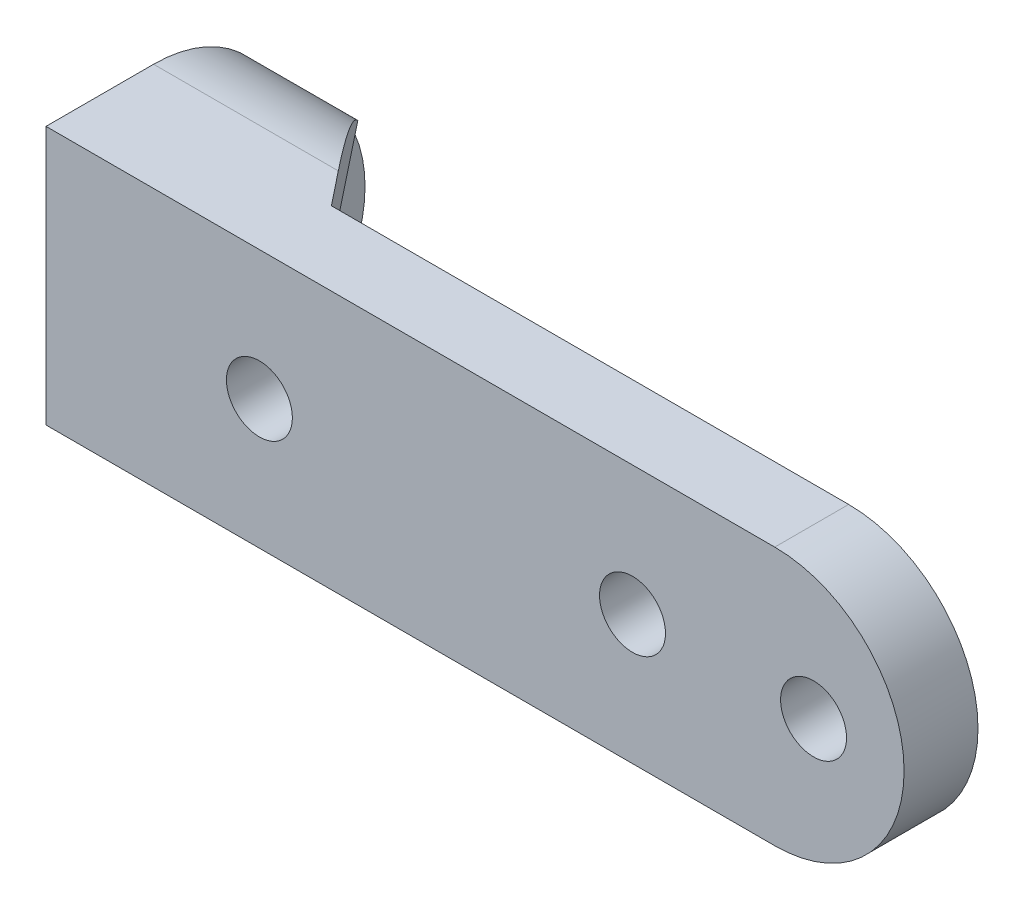
SolidWorks part; units mm, degrees
ref_plane "Front Plane" through (0, 0, 0) normal (0, 0, 1) x (1, 0, 0)
ref_plane "Top Plane" through (0, 0, 0) normal (0, 1, 0) x (1, 0, 0)
ref_plane "Right Plane" through (0, 0, 0) normal (1, 0, 0) x (0, 0, -1)
sketch "Sketch2" plane through (0, 0, 0) normal (0, 0, 1) x (1, 0, 0)
  line L0 (-20, 0) -> (20, 0) construction
  line L1 (-20, 10) -> (20, 10)
  line L2 (-20, -10) -> (20, -10)
  line L4 (-20, 10) -> (-30, 10)
  line L5 (-20, 10) -> (-20, -10)
  line L6 (-20, -10) -> (-30, -10)
  line L7 (-30, 10) -> (-30, -10)
  arc A0 (-20, 10) -> (-20, -10) centre (-20, 0) ccw
  arc A1 (20, -10) -> (20, 10) centre (20, 0) ccw
  point P2 (0, 0)
  dimension "D1" = 20
  dimension "D2" = 60
extrude "Boss-Extrude1" add sketch "Sketch2" along normal mid plane 5.715 contours A0 L4 L7 | L5 A0 | A0 L7 L6 | L2 A1 L1 L5 region at (-27.7663, 7.7663, 0) region at (3.979, 0, 0) region at (-24.2441, 0, 0) region at (-27.7663, -7.7663, 0)
sketch "Sketch3" plane through (0, 0, 2.8575) normal (0, 0, 1) x (1, 0, 0)
  line L0 (30, 0) -> (23, 0) construction
  line L1 (23, 0) -> (9, 0) construction
  circle A1 centre (9, 0) radius 2.55
  circle A2 centre (23, 0) radius 2.55
  arc A3 (20, -10) -> (20, 10) centre (20, 0) ccw construction
  dimension "D1" = 5.1
  dimension "D2" = 7
  dimension "D3" = 14
extrude "Cut-Extrude1" cut sketch "Sketch3" against normal through all both and the other way through all from surface starting at face at (-2.5, 0, 2.8575)
sketch "Sketch4" plane through (0, 0, 2.8575) normal (0, 0, 1) x (1, 0, 0)
  circle A0 centre (-19.85, 0) radius 2.55
  dimension "D1" = 5.1
  dimension "D2" = 19.85
extrude "Cut-Extrude2" cut sketch "Sketch4" against normal up to surface (5.715 mm away) up to face at (11.55, 0, -2.8575)
sketch "Sketch5" plane through (-30, 0, 0) normal (-1, 0, 0) x (0, 0, 1)
  line L0 (2.8575, -10) -> (-2.8575, -10) construction
  line L1 (2.8575, 10) -> (-15.4613, 10)
  line L2 (2.8575, 10) -> (2.8575, -10)
  line L3 (2.8575, -10) -> (-15.4613, -10)
  line L4 (-15.4613, 10) -> (-15.4613, -10)
extrude "Boss-Extrude2" add sketch "Sketch5" along normal blind 6.35
fillet "Fillet1" radius 10 2 edges at (-33.175, -10, -15.4613) (-33.175, 10, -15.4613)
sketch "Sketch6" plane through (-36.35, 0, 0) normal (-1, 0, 0) x (0, 0, 1)
  line L0 (2.8575, 10) -> (2.8575, -10) construction
  circle A0 centre (-9.1425, 0) radius 2.55
  dimension "D2" = 5.1
  dimension "D1" = 12
extrude "Cut-Extrude3" cut sketch "Sketch6" against normal through all both and the other way through all
sketch "Sketch7" plane through (0, 10, 0) normal (0, 1, 0) x (1, 0, 0)
  line L0 (-20, 2.8575) -> (-30, 15.4613)
  line L1 (20, 2.8575) -> (-30, 2.8575) construction
  line L2 (-30, 2.8575) -> (-30, 5.4613) construction
  line L3 (-30, 5.4613) -> (-30, 15.4613) construction
  line L4 (20, 2.8575) -> (-30, 2.8575)
  line L5 (-30, 2.8575) -> (-30, 5.4613)
  line L6 (-30, 5.4613) -> (-30, 15.4613)
  line M1 (-30, 2.8575) -> (-30, 5.4613)
  line M6 (20, 2.8575) -> (-30, 2.8575)
  dimension "D1" = 10
extrude "Boss-Extrude3" add sketch "Sketch7" against normal blind 3.175 contours L6 L0 M1 M6 region at (-26.6667, 10, -7.0588)
mirror "Mirror1" about plane through (0, 0, 0) normal (0, 1, 0) of "Boss-Extrude3"
sketch "Sketch8" plane through (-36.35, 0, 0) normal (-1, 0, 0) x (0, 0, 1)
  line L1 (-5.4613, 10) -> (-15.4613, 10)
  line L2 (-5.4613, 10) -> (-5.4613, -10)
  line L3 (-5.4613, -10) -> (2.8575, -10)
  line L4 (2.8575, -10) -> (2.8575, 10)
  line L5 (2.8575, 10) -> (-5.4613, 10)
  line L6 (-5.4613, -10) -> (2.8575, -10)
  line L7 (2.8575, -10) -> (2.8575, 10)
  line L8 (2.8575, 10) -> (-5.4613, 10)
  line L9 (-5.4613, -10) -> (-15.4613, -10)
  line L10 (-15.4613, 10) -> (-15.4613, -10)
  arc A2 (-5.4613, 10) -> (-15.4613, 0) centre (-5.4613, 0) ccw
  arc A3 (-15.4613, 0) -> (-5.4613, -10) centre (-5.4613, 0) ccw
  arc A4 (-5.4613, 10) -> (-15.4613, 0) centre (-5.4613, 0) ccw
  arc A5 (-15.4613, 0) -> (-5.4613, -10) centre (-5.4613, 0) ccw
  arc M7 (-5.4613, 10) -> (-15.4613, 0) centre (-5.4613, 0) ccw
  arc M8 (-15.4613, 0) -> (-5.4613, -10) centre (-5.4613, 0) ccw
  dimension "D1" = 0
extrude "Cut-Extrude4" cut sketch "Sketch8" against normal through all both and the other way through all contours L1 L10 M7 | L10 L9 M8 region at (-36.35, 7.7663, -13.2277) region at (-36.35, -7.7663, -13.2277)
fillet "Fillet2" radius 2 5 edges at (-30, 6.825, -7.8138) (-30, -6.825, -7.8138) (-30, 0, -2.8575) (-25, 6.825, -2.8575) (-25, -6.825, -2.8575)
equation "\"PullyHoldDiameter\"=5.1"
equation "\"D1@Sketch4\"=\"PullyHoldDiameter\""
equation "\"PullyPlateLength\"=60"
equation "\"D2@Sketch2\"=\"PullyPlateLength\""
